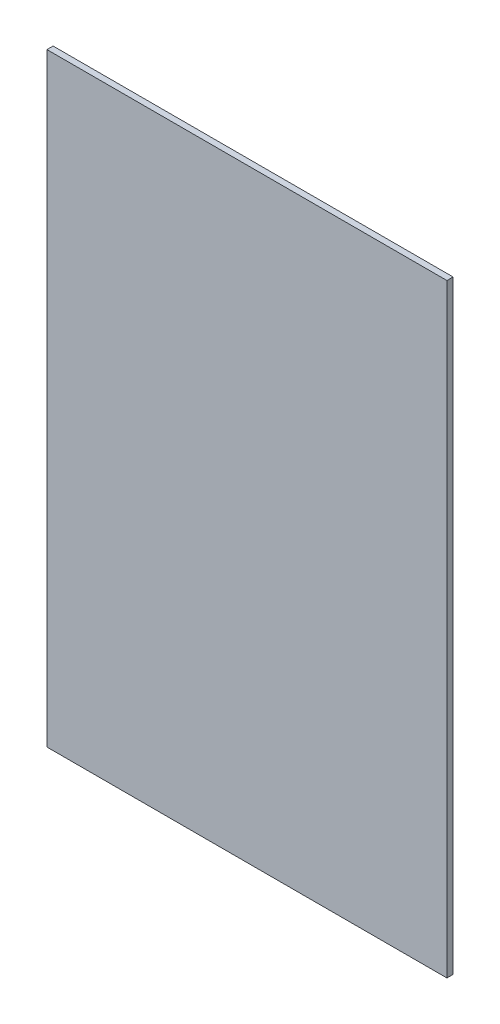
SolidWorks part; units mm, degrees
ref_plane "Спереди" through (0, 0, 0) normal (0, 0, 1) x (1, 0, 0)
ref_plane "Сверху" through (0, 0, 0) normal (0, 1, 0) x (1, 0, 0)
ref_plane "Справа" through (0, 0, 0) normal (1, 0, 0) x (0, 0, -1)
sketch "Sketch1" plane through (0, 0, 0) normal (0, 0, 1) x (1, 0, 0)
  line L0 (-110, 0) -> (-130, 0) construction
  line L5 (-130, 130) -> (130, 130)
  line L6 (-130, 130) -> (-130, -262.6)
  line L7 (-130, -262.6) -> (130, -262.6)
  line L8 (130, 130) -> (130, -262.6)
  line L9 (0, 110) -> (0, 130) construction
  line L10 (110, 0) -> (130, 0) construction
  line L12 (-19.4, -262.4) -> (-13.9, -262.4) construction
  circle A8 centre (0, 0) radius 110 construction
  circle A9 centre (0, 0) radius 110 construction
  circle A10 centre (0, 0) radius 110 construction
  circle A11 centre (0, 0) radius 110 construction
  dimension "D1" = 20
  dimension "D2" = 0.2
extrude "Extrude1" add sketch "Sketch1" along normal blind 4
equation "\"thickness\"=4"
equation "\"D1@Extrude1\"= \"thickness\""
equation "\"pin_l\"=5"
equation "\"pin_skew\"=4"
equation "\"pin_r\"=5"
equation "\"M4_plastic_thread\"=3.8"
equation "\"M3_plastic_thread\" = 2.8"
equation "\"min_d\"=0.2"
equation "\"D2@Sketch1\"=\"min_d\""
